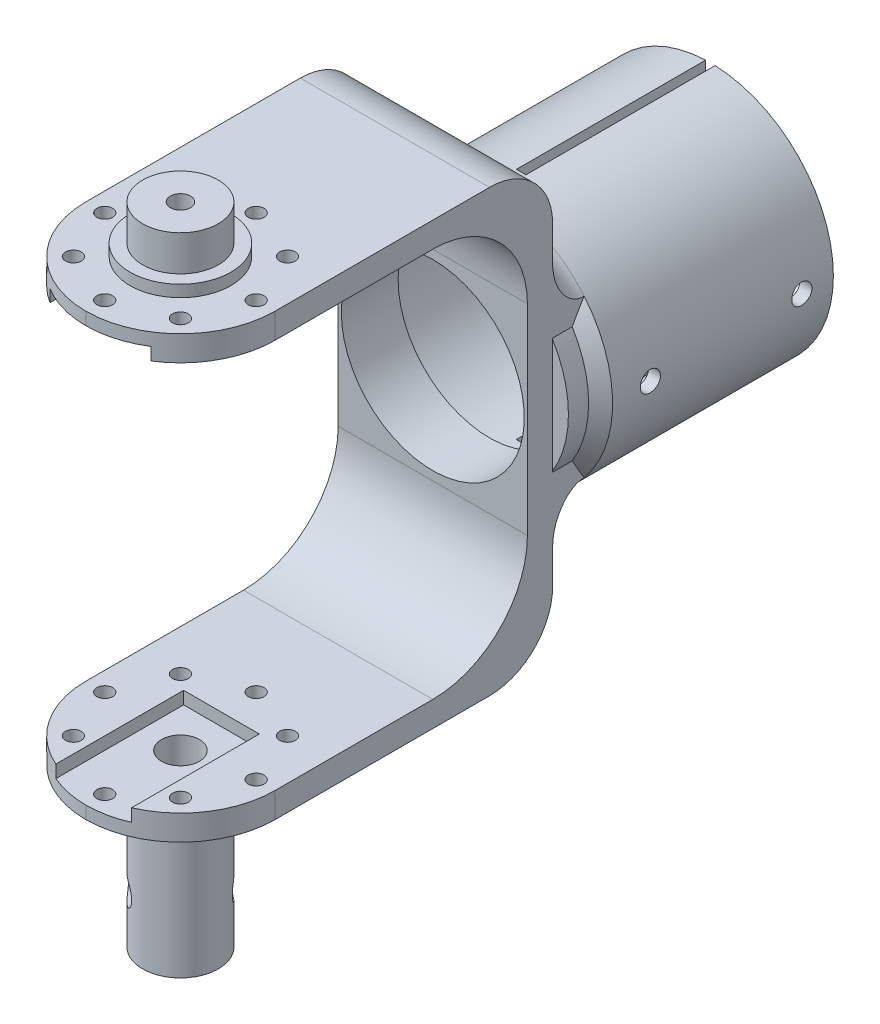
SolidWorks part; units mm, degrees
ref_plane "前视基准面" through (0, 0, 0) normal (0, 0, 1) x (1, 0, 0)
ref_plane "上视基准面" through (0, 0, 0) normal (0, 1, 0) x (1, 0, 0)
ref_plane "右视基准面" through (0, 0, 0) normal (1, 0, 0) x (0, 0, -1)
sketch "草图1" plane through (0, 0, 0) normal (1, 0, 0) x (0, 0, -1)
  line L0 (-27.5, 34.9) -> (31.5, 34.9)
  line L1 (-27.5, 30.9) -> (27.5, 30.9)
  line L2 (31.5, 34.9) -> (31.5, -34.9)
  line L3 (-27.5, -30.9) -> (27.5, -30.9)
  line L4 (27.5, 30.9) -> (27.5, -30.9)
  line L5 (-27.5, 30.9) -> (27.5, -30.9) construction
  line L6 (-27.5, -30.9) -> (27.5, 30.9) construction
  line L7 (-27.5, -34.9) -> (31.5, -34.9)
  line L8 (-27.5, 34.9) -> (-27.5, 30.9)
  line L9 (-27.5, -30.9) -> (-27.5, -34.9)
  point P0 (0, 0)
  dimension "D1" = 61.8
  dimension "D2" = 55
  dimension "D4" = 55
  dimension "D3" = 4
extrude "凸台-拉伸1" add sketch "草图1" along normal blind 30
sketch "草图4" plane through (0, 34.9, 0) normal (0, 1, 0) x (1, 0, 0)
  line L0 (30, 31.5) -> (30, -27.5) construction
  line L1 (30, -27.5) -> (0, -27.5) construction
  circle A0 centre (15, -12.5) radius 12 construction
  circle A1 centre (15, -0.5) radius 1.25
  circle A2 centre (15, -12.5) radius 12 construction
  circle A3 centre (23.4853, -4.0147) radius 1.25
  circle A4 centre (15, -12.5) radius 12 construction
  circle A5 centre (27, -12.5) radius 1.25
  circle A6 centre (15, -12.5) radius 12 construction
  circle A7 centre (23.4853, -20.9853) radius 1.25
  circle A8 centre (15, -12.5) radius 12 construction
  circle A9 centre (15, -24.5) radius 1.25
  circle A10 centre (15, -12.5) radius 12 construction
  circle A11 centre (6.5147, -20.9853) radius 1.25
  circle A12 centre (15, -12.5) radius 12 construction
  circle A13 centre (3, -12.5) radius 1.25
  circle A14 centre (15, -12.5) radius 12 construction
  circle A15 centre (6.5147, -4.0147) radius 1.25
  circle A16 centre (15, -12.5) radius 1.6
  point P31 (15, -12.5)
  dimension "D2" = 15
  dimension "D3" = 24
  dimension "D4" = 2.5
  dimension "D6" = 3.2
  dimension "D1" = 15
  dimension "D5" = 8
extrude "切除-拉伸1" cut sketch "草图4" against normal through all
fillet "圆角1" radius 15 6 edges at (0, 32.9, 27.5) (30, 32.9, 27.5) (30, -32.9, 27.5) (0, -32.9, 27.5) (15, -30.9, -27.5) (15, 30.9, -27.5)
fillet "圆角2" radius 10 2 edges at (15, -34.9, -31.5) (15, 34.9, -31.5)
sketch "草图5" plane through (0, 0, -31.5) normal (0, 0, -1) x (-1, 0, 0)
  line L0 (-30, -24.9) -> (-30, 24.9) construction
  circle A0 centre (-15, 0) radius 17.6
  circle A1 centre (-15, 0) radius 19.5
  dimension "D2" = 35.2
  dimension "D3" = 39
  dimension "D1" = 15
extrude "凸台-拉伸2" add sketch "草图5" along normal blind 40
sketch "草图7" plane through (0, 0, -71.5) normal (0, 0, -1) x (-1, 0, 0)
  line L1 (-15.75, 42.3131) -> (-14.25, 42.3131)
  line L2 (-15.75, 42.3131) -> (-15.75, -42.3131)
  line L3 (-15.75, -42.3131) -> (-14.25, -42.3131)
  line L4 (-14.25, 42.3131) -> (-14.25, -42.3131)
  line L5 (-15.75, 42.3131) -> (-14.25, -42.3131) construction
  line L6 (-15.75, -42.3131) -> (-14.25, 42.3131) construction
  point P0 (-15, 0)
  dimension "D1" = 1.5
extrude "切除-拉伸3" cut sketch "草图7" against normal blind 30
sketch "草图8" plane through (0, 0, 0) normal (1, 0, 0) x (0, 0, -1)
  line L0 (-977.5, 0) -> (49022.5, 0) construction
  line L1 (27.5, 15.9) -> (27.5, -15.9) construction
  line L2 (71.5, -19.4856) -> (71.5, 19.4856) construction
  line L3 (27.5, 15.9) -> (27.5, -15.9) construction
  circle A0 centre (66.5, 0) radius 1.6
  circle A1 centre (42.5, 0) radius 1.6
  point P5 (27.5, 0)
  dimension "D1" = 3.2
  dimension "D2" = 15
  dimension "D3" = 5
  dimension "D4" = 3.2
extrude "切除-拉伸4" cut sketch "草图8" along normal through all and the other way blind 8
sketch "草图10" plane through (0, 0, -31.5) normal (0, 0, -1) x (-1, 0, 0)
  circle A0 centre (-15, 0) radius 17.5
extrude "凸台-拉伸4" add sketch "草图10" along normal blind 5
chamfer "倒角2" distance 5 angle 45 2 edges at (34.5, 0, -31.5) (-4.5, 0, -31.5)
sketch "草图11" plane through (0, -34.9, 0) normal (0, -1, 0) x (1, 0, 0)
  circle A0 centre (15, 12.5) radius 8
  circle A1 centre (15, 12.5) radius 3
  dimension "D1" = 16
  dimension "D2" = 6
extrude "凸台-拉伸5" add sketch "草图11" along normal blind 25
sketch "草图12" plane through (0, -59.9, 0) normal (0, -1, 0) x (1, 0, 0)
  circle A0 centre (15, 12.5) radius 6
  dimension "D1" = 12
extrude "切除-拉伸5" cut sketch "草图12" against normal blind 23.15 flip side to cut
sketch "草图15" plane through (0, 34.9, 0) normal (0, 1, 0) x (1, 0, 0)
  circle A0 centre (15, -12.5) radius 8
  circle A1 centre (15, -12.5) radius 1.6
  dimension "D1" = 16
  dimension "D2" = 3.2
extrude "凸台-拉伸6" add sketch "草图15" along normal blind 7.5
sketch "草图16" plane through (0, 42.4, 0) normal (0, 1, 0) x (1, 0, 0)
  circle A0 centre (15, -12.5) radius 6
  dimension "D1" = 12
extrude "切除-拉伸6" cut sketch "草图16" against normal blind 5.65 flip side to cut
fillet "圆角3" radius 5 2 edges at (15, 19.5, -31.5) (15, -19.5, -31.5)
sketch "草图17" plane through (0, -34.9, 0) normal (0, -1, 0) x (1, 0, 0)
  circle A0 centre (15, 12.5) radius 3 construction
  circle A1 centre (15, 12.5) radius 3
extrude "切除-拉伸7" cut sketch "草图17" against normal blind 8
ref_plane "基准面1" through (0, 0, 12.5) normal (0, 0, -1) x (-1, 0, 0)
sketch "草图19" plane through (0, 0, 12.5) normal (0, 0, -1) x (-1, 0, 0)
  line L0 (0, 30.9) -> (-30, 30.9) construction
  line L1 (-7, 32.9) -> (-23, 32.9)
  line L2 (-7, 32.9) -> (-7, 28.9)
  line L3 (-7, 28.9) -> (-23, 28.9)
  line L4 (-23, 32.9) -> (-23, 28.9)
  line L5 (-7, 32.9) -> (-23, 28.9) construction
  line L6 (-7, 28.9) -> (-23, 32.9) construction
  line L7 (-30, -30.9) -> (0, -30.9) construction
  line L8 (-9, -32.9) -> (-21, -32.9)
  line L9 (-9, -32.9) -> (-9, -28.9)
  line L10 (-9, -28.9) -> (-21, -28.9)
  line L11 (-21, -32.9) -> (-21, -28.9)
  line L12 (-9, -32.9) -> (-21, -28.9) construction
  line L13 (-9, -28.9) -> (-21, -32.9) construction
  point P0 (-15, 30.9)
  point P7 (-15, -30.9)
  dimension "D1" = 12
  dimension "D2" = 4
  dimension "D3" = 16
  dimension "D4" = 4
extrude "切除-拉伸8" cut sketch "草图19" against normal blind 20 and the other way blind 6.5
sketch "草图20" plane through (0, 0, -36.5) normal (0, 0, -1) x (-1, 0, 0)
  circle A2 centre (-15, 0) radius 14.5
  circle A3 centre (-15, 0) radius 14.5
  dimension "D1" = 3
extrude "切除-拉伸9" cut sketch "草图20" against normal blind 20
ref_axis "基准轴1" through (15, -59.9, 12.5) along (0, 1, 0)
ref_plane "基准面2" through (1.25, 0, -1.25) normal (-0.7071, 0, 0.7071) x (0, 1, 0)
ref_plane "基准面3" through (0, -51.75, 0) normal (0, -1, 0) x (-1, 0, 0)
sketch "草图21" plane through (0, -51.75, 0) normal (0, -1, 0) x (-1, 0, 0)
  line L0 (-15, -12.5) -> (-15, 15.533)
  line L1 (-15, -12.5) -> (-33.3603, 9.381)
  dimension "D1" = 40
ref_plane "基准面4" through (33.3603, -51.75, -9.381) normal (0.6428, 0, -0.766) x (-0.766, 0, -0.6428)
sketch "草图22" plane through (33.3603, -51.75, -9.381) normal (0.6428, 0, -0.766) x (-0.766, 0, -0.6428)
  circle A0 centre (0, 0) radius 2
  point P2 (0, 0)
  dimension "D1" = 4
extrude "切除-拉伸10" cut sketch "草图22" against normal through all
